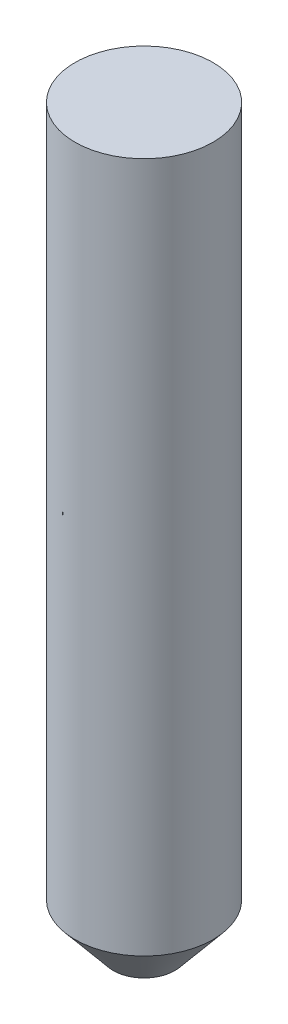
SolidWorks part; units mm, degrees
ref_plane "Front Plane" through (0, 0, 0) normal (0, 0, 1) x (1, 0, 0)
ref_plane "Top Plane" through (0, 0, 0) normal (0, 1, 0) x (1, 0, 0)
ref_plane "Right Plane" through (0, 0, 0) normal (1, 0, 0) x (0, 0, -1)
sketch "Sketch1" plane through (0, 0, 0) normal (0, 0, 1) x (1, 0, 0)
  line L0 (0, -943.5188) -> (0, 46232.4233) construction
  line L1 (0, 0) -> (-15, 0)
  line L2 (-15, 0) -> (-15, -150)
  line L3 (-15, -150) -> (-6.6934, -160)
  line L4 (-6.6934, -160) -> (-4.6934, -160)
  line L5 (0, -10) -> (-12.5, -10)
  line L6 (-12.5, -10) -> (-12.5, -150)
  line L7 (-12.5, -150) -> (-6.3356, -158.5)
  line L8 (-6.3356, -158.5) -> (-4.6934, -158.5)
  line L9 (-12.5, -140) -> (0, -140)
  line L10 (-4.6934, -158.5) -> (-4.6934, -160)
  line L11 (-12.5, -140) -> (-15, -140)
  line L12 (-12.5, -10) -> (-15, -10)
  point P8 (-4.5027, -156.6993)
  point P18 (-5.6141, -157.5)
  point P19 (-6.1308, -157.5)
  point P20 (-4.6934, -159.25)
  point P21 (-7.729, -158.5)
  point P22 (-6.6934, -158.5)
  point P23 (0, 0)
  dimension "D1" = 15
  dimension "D2" = 150
  dimension "D3" = 1.5
  dimension "D4" = 10
  dimension "D5" = 2.5
  dimension "D6" = 10
  dimension "D7" = 13
  dimension "D8" = 2
  dimension "D9" = 130
  dimension "D10" = 10.5
revolve "Revolve1" add sketch "Sketch1" angle 360 about L0 region at (-7.5, -5, 0) region at (-12.725, -145, 0)
revolve "Revolve2" add sketch "Sketch1<5>" angle 260 about L0 region at (-13.75, -75, 0)
sketch "Sketch1<5>" plane through (0, 0, 0) normal (0, 0, 1) x (1, 0, 0) same geometry as "Sketch1"
